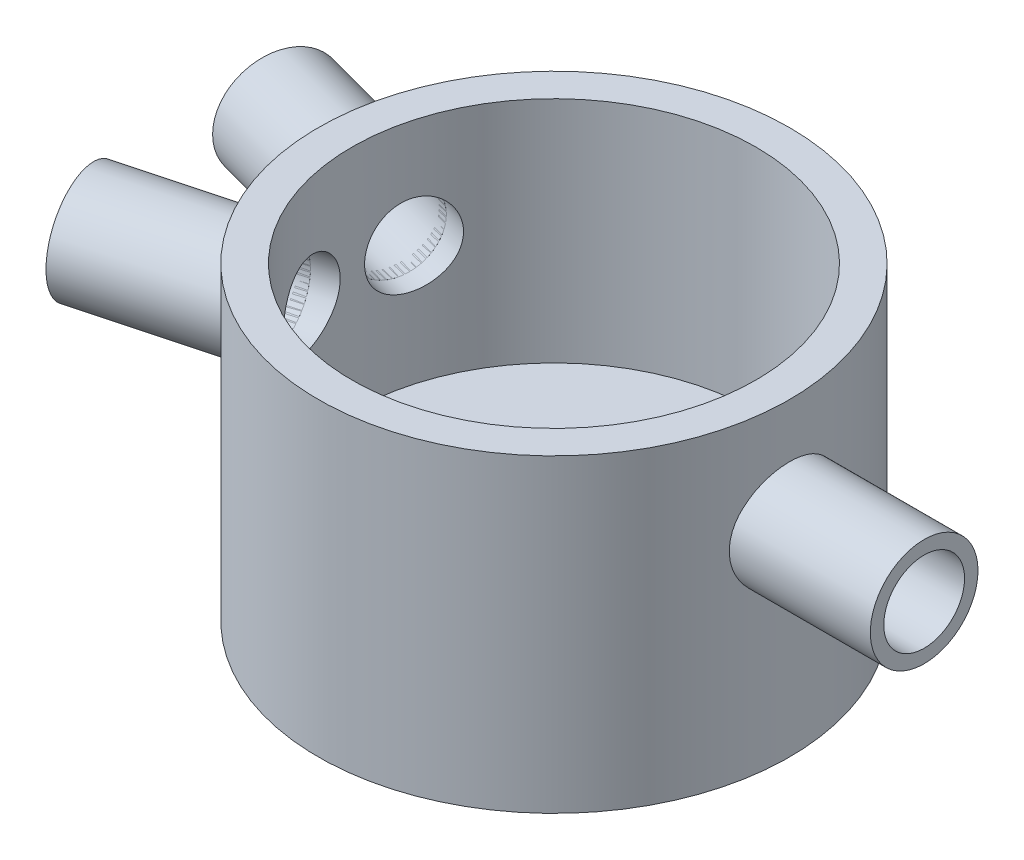
SolidWorks part; units mm, degrees
ref_plane "Plano frontal" through (0, 0, 0) normal (0, 0, 1) x (1, 0, 0)
ref_plane "Plano superior" through (0, 0, 0) normal (0, 1, 0) x (1, 0, 0)
ref_plane "Plano direito" through (0, 0, 0) normal (1, 0, 0) x (0, 0, -1)
sketch "Esboço1" plane through (0, 0, 0) normal (0, 0, 1) x (1, 0, 0)
  line L0 (0, 0) -> (0, 24.7405) construction
  line L1 (0, 0) -> (30.393, 0) construction
  line L2 (0, -15) -> (17.5, -15)
  line L3 (17.5, -15) -> (17.5, 8)
  line L4 (17.5, 8) -> (15, 8)
  line L5 (15, 8) -> (15, -9)
  line L6 (15, -9) -> (5, -9)
  line L7 (5, -9) -> (5, -11.5)
  line L8 (5, -11.5) -> (3.25, -11.5)
  line L9 (0, -12.5) -> (0, -15)
  line L10 (3.25, -11.5) -> (3.25, -12.5)
  line L11 (3.25, -12.5) -> (0, -12.5)
  dimension "D1" = 35
  dimension "D2" = 30
  dimension "D3" = 2.5
  dimension "D4" = 23
  dimension "D5" = 8
  dimension "D6" = 3.5
  dimension "D7" = 6.5
  dimension "D8" = 10
  dimension "D9" = 9
revolve "Revolução1" add sketch "Esboço1" angle 360 about L0
sketch "Esboço4" plane through (0, 0, 0) normal (1, 0, 0) x (0, 0, -1)
  point P0 (0, 0)
hole_wizard "Furos-guia com Ø6.0mm1" positions "3DSketch2" profile "Esboço5" hole size "Ø6.0" standard "Ansi Metric"
sketch3d "3DSketch2"
  point P0 (17.5, 0, 0)
sketch "Esboço5" plane through (17.5, 0, 0) normal (0, 1, 0) x (0, 0, -1)
  line L0 (0, 0) -> (0, 6.8026)
  line L1 (0, 6.8026) -> (3, 5)
  line L2 (3, 5) -> (3, 0)
  line L5 (3, 0) -> (0, 0)
  line L10 (0, 6.8026) -> (-3, 5) construction
  line L11 (0, -6.35) -> (0, 107.95) construction
  dimension "Hole Dia." = 6
  dimension "Hole Depth" = 5
  dimension "Drill Angle" = 118
sketch "Esboço6" plane through (0, 0, 0) normal (0, 1, 0) x (1, 0, 0)
  line L0 (0, 0) -> (-19.9458, -5.3445)
  line L1 (0, 0) -> (-27.9467, 7.4883)
  line L2 (0, 0) -> (-25.073, 0) construction
  dimension "D1" = 15
  dimension "D2" = 15
hole_wizard "Furos-guia com Ø6.0mm5" positions "3DSketch3" profile "Esboço7" hole size "Ø6.0" standard "Ansi Metric"
sketch3d "3DSketch3"
  line L0 (0, 0, 0) -> (-27.9467, 0, -7.4883) construction
  point P0 (-16.9037, 0, -4.5293)
sketch "Esboço7" plane through (-16.9037, 0, -4.5293) normal (0, 1, 0) x (-0.2588, 0, 0.9659)
  line L0 (0, 0) -> (0, 6.8026)
  line L1 (0, 6.8026) -> (3, 5)
  line L2 (3, 5) -> (3, 0)
  line L5 (3, 0) -> (0, 0)
  line L10 (0, 6.8026) -> (-3, 5) construction
  line L11 (0, -6.35) -> (0, 107.95) construction
  dimension "Hole Dia." = 6
  dimension "Hole Depth" = 5
  dimension "Drill Angle" = 118
hole_wizard "Furos-guia com Ø6.0mm4" positions "3DSketch4" profile "Esboço8" hole size "Ø6.0" standard "Ansi Metric"
sketch3d "3DSketch4"
  line L0 (0, 0, 0) -> (-19.9458, 0, 5.3445) construction
  point P0 (-16.9037, 0, 4.5293)
sketch "Esboço8" plane through (-16.9037, 0, 4.5293) normal (0, 1, 0) x (0.2588, 0, 0.9659)
  line L0 (0, 0) -> (0, 6.8026)
  line L1 (0, 6.8026) -> (3, 5)
  line L2 (3, 5) -> (3, 0)
  line L5 (3, 0) -> (0, 0)
  line L10 (0, 6.8026) -> (-3, 5) construction
  line L11 (0, -6.35) -> (0, 107.95) construction
  dimension "Hole Dia." = 6
  dimension "Hole Depth" = 5
  dimension "Drill Angle" = 118
ref_plane "Plano1" through (-16.9037, 0, -4.5293) normal (-0.9659, 0, -0.2588) x (0, -1, 0)
sketch "Esboço9" plane through (-16.9037, 0, -4.5293) normal (-0.9659, 0, -0.2588) x (0, -1, 0)
  circle A0 centre (0, 0) radius 3
  circle A1 centre (0, 0) radius 4
  dimension "D1" = 1
  dimension "D2" = 6
extrude "Ressalto-extrusão1" add sketch "Esboço9" along normal up to vertex (11.4326 mm away) and the other way blind 1 separate body up to point (-27.9467, 0, -7.4883)
ref_plane "Plano2" through (-16.9037, 0, 4.5293) normal (-0.9659, 0, 0.2588) x (0, -1, 0)
sketch "Esboço11" plane through (-16.9037, 0, 4.5293) normal (-0.9659, 0, 0.2588) x (0, -1, 0)
  circle A0 centre (0, 0) radius 3
  circle A1 centre (0, 0) radius 4
  dimension "D1" = 1
  dimension "D2" = 6
extrude "Ressalto-extrusão2" add sketch "Esboço11" against normal blind 1 and the other way blind 11 separate body
ref_plane "Plano3" through (17.5, 0, 0) normal (1, 0, 0) x (0, -1, 0)
sketch "Esboço13" plane through (17.5, 0, 0) normal (1, 0, 0) x (0, -1, 0)
  circle A0 centre (0, 0) radius 3
  circle A1 centre (0, 0) radius 4
  dimension "D1" = 6
  dimension "D2" = 1
extrude "Ressalto-extrusão3" add sketch "Esboço13" against normal blind 1 and the other way blind 10 separate body
